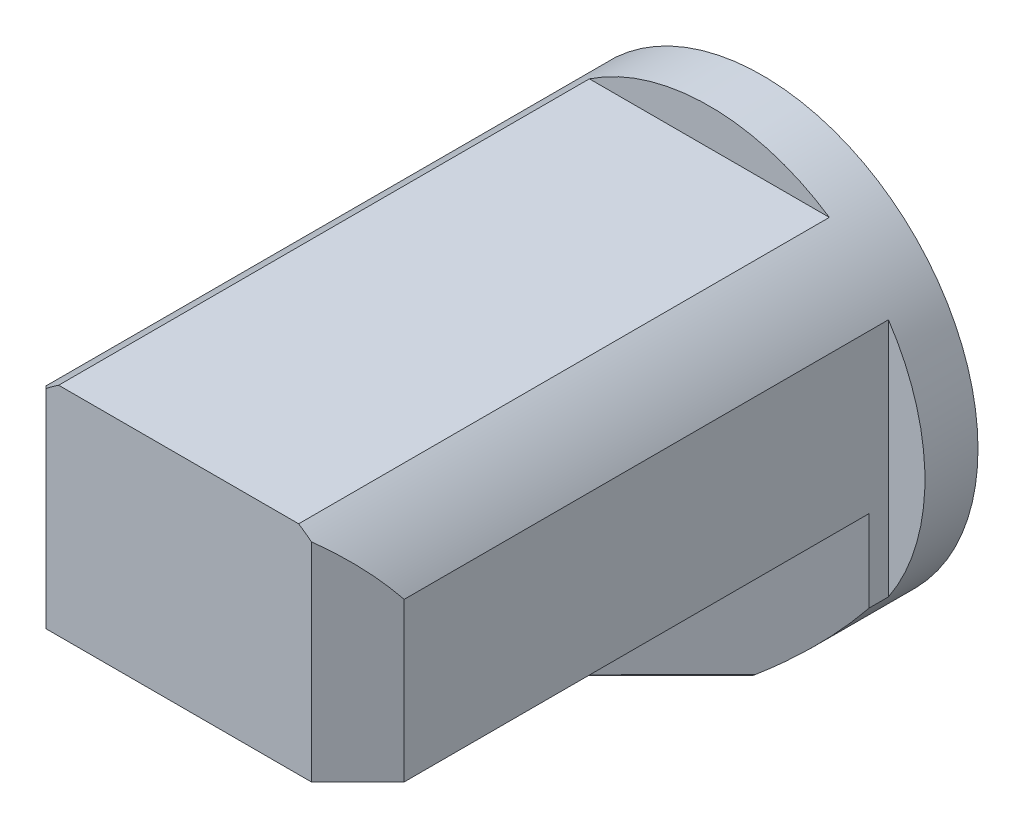
SolidWorks part; units mm, degrees
material "Cast Stainless Steel"
ref_plane "Front Plane" through (0, 0, 0) normal (0, 0, 1) x (1, 0, 0)
ref_plane "Top Plane" through (0, 0, 0) normal (0, 1, 0) x (1, 0, 0)
ref_plane "Right Plane" through (0, 0, 0) normal (1, 0, 0) x (0, 0, -1)
sketch "Sketch3" plane through (0, 0, 0) normal (0, 1, 0) x (1, 0, 0)
  circle A0 centre (0, 0) radius 130
extrude "Boss-Extrude1" add sketch "Sketch3" along normal blind 352
sketch "Sketch11" plane through (0, 352, 0) normal (0, 1, 0) x (1, 0, 0)
  line L0 (0, 0) -> (0, -108)
  line L1 (-72.3602, -108) -> (72.3602, -108)
  line L2 (0, 0) -> (-54.0967, 0)
  line L3 (-72.3602, 108) -> (72.3602, 108)
  line L4 (0, 0) -> (0, 40.1674)
  line L5 (0, 0) -> (108, 0)
  line L6 (108, 72.3602) -> (108, -72.3602)
  line L7 (-108, 72.3602) -> (-108, -72.3602)
  circle A0 centre (0, 0) radius 130 construction
  circle A2 centre (0, 0) radius 130
  circle A3 centre (0, 0) radius 130
  circle M1 centre (0, 0) radius 130
  dimension "D1" = 0
extrude "Cut-Extrude2" cut sketch "Sketch11" against normal blind 320 contours L1 M1 | L3 M1 region at (0, 352, 116.8671) region at (0, 352, -116.8671)
extrude "Cut-Extrude3" cut sketch "Sketch11<4>" against normal blind 320 contours L7 M1 | L6 M1 region at (116.8671, 352, 0) region at (-116.8671, 352, 0)
sketch "Sketch11<4>" plane through (0, 352, 0) normal (0, 1, 0) x (1, 0, 0) same geometry as "Sketch11"
sketch "Sketch12" plane through (-108, 0, 0) normal (-1, 0, 0) x (0, 0, 1)
  line L0 (0, 32) -> (0, 137)
  line L1 (-72.3602, 32) -> (72.3602, 32) construction
  line L2 (-72.3602, 137) -> (72.3602, 137)
  line L3 (-72.3602, 32) -> (-72.3602, 352) construction
  line L4 (72.3602, 32) -> (72.3602, 352) construction
  line L5 (72.3602, 32) -> (72.3602, 352)
  line L6 (-72.3602, 32) -> (-72.3602, 352)
  line L7 (-72.3602, 352) -> (72.3602, 352) construction
  line L8 (-72.3602, 352) -> (72.3602, 352)
  line L13 (72.3602, 352) -> (-72.3602, 352)
  line L14 (-72.3602, 352) -> (-72.3602, 32)
  line L15 (-72.3602, 32) -> (72.3602, 32)
  line L16 (72.3602, 32) -> (72.3602, 352)
  line L17 (72.3602, 352) -> (-72.3602, 352)
  line L18 (-72.3602, 352) -> (-72.3602, 32)
  line L19 (-72.3602, 32) -> (72.3602, 32)
  line L20 (72.3602, 32) -> (72.3602, 352)
  line M2 (72.3602, 352) -> (-72.3602, 352)
  line M3 (-72.3602, 352) -> (-72.3602, 32)
  line M5 (72.3602, 32) -> (72.3602, 352)
  dimension "D1" = 0
extrude "Cut-Extrude4" cut sketch "Sketch12" against normal blind 85 contours L2 M3 M5 M2 region at (-108, 244.5, 0)
sketch "Sketch14" plane through (-108, 0, 0) normal (-1, 0, 0) x (0, 0, 1)
  line L0 (-14.6151, 137) -> (14.6151, 137)
  line L1 (-72.3602, 137) -> (72.3602, 137) construction
  line L2 (14.6151, 137) -> (72.3602, 79.2549)
  line L3 (72.3602, 32) -> (72.3602, 137) construction
  line L4 (0, 137) -> (0, 116.7059)
  line L5 (-14.6151, 137) -> (-72.3602, 79.2549)
  line L10 (72.3602, 137) -> (-72.3602, 137)
  line L11 (-72.3602, 137) -> (-72.3602, 32)
  line L12 (-72.3602, 32) -> (72.3602, 32)
  line L13 (72.3602, 32) -> (72.3602, 137)
  line L14 (72.3602, 137) -> (-72.3602, 137)
  line L15 (-72.3602, 137) -> (-72.3602, 32)
  line L16 (-72.3602, 32) -> (72.3602, 32)
  line L17 (72.3602, 32) -> (72.3602, 137)
  line M8 (72.3602, 137) -> (-72.3602, 137)
  line M9 (-72.3602, 137) -> (-72.3602, 32)
  line M11 (72.3602, 32) -> (72.3602, 137)
  dimension "D1" = 0
extrude "Cut-Extrude5" cut sketch "Sketch14" against normal blind 85 contours L5 M8 M9 | L2 M8 M11 region at (-108, 117.7516, -53.1118) region at (-108, 117.7516, 53.1118)
sketch "Sketch15" plane through (0, 352, 0) normal (0, 1, 0) x (1, 0, 0)
  line L0 (-23, -72.3602) -> (-23, -108)
  line L1 (-72.3602, -108) -> (72.3602, -108) construction
  line L2 (-23, 72.3602) -> (-23, 108)
  line L3 (-72.3602, 108) -> (72.3602, 108) construction
  line L10 (-108, 72.3602) -> (-23, 72.3602)
  line L11 (-23, 72.3602) -> (-23, -72.3602)
  line L12 (-23, -72.3602) -> (-108, -72.3602)
  line L13 (-72.3602, -108) -> (72.3602, -108)
  line L14 (108, -72.3602) -> (108, 72.3602)
  line L15 (72.3602, 108) -> (-72.3602, 108)
  line L16 (-108, 72.3602) -> (-23, 72.3602)
  line L17 (-23, 72.3602) -> (-23, -72.3602)
  line L18 (-23, -72.3602) -> (-108, -72.3602)
  line L19 (-72.3602, -108) -> (72.3602, -108)
  line L20 (108, -72.3602) -> (108, 72.3602)
  line L21 (72.3602, 108) -> (-72.3602, 108)
  arc A4 (-108, -72.3602) -> (-72.3602, -108) centre (0, 0) ccw
  arc A5 (72.3602, -108) -> (108, -72.3602) centre (0, 0) ccw
  arc A6 (108, 72.3602) -> (72.3602, 108) centre (0, 0) ccw
  arc A7 (-72.3602, 108) -> (-108, 72.3602) centre (0, 0) ccw
  arc A8 (-108, -72.3602) -> (-72.3602, -108) centre (0, 0) ccw
  arc A9 (72.3602, -108) -> (108, -72.3602) centre (0, 0) ccw
  arc A10 (108, 72.3602) -> (72.3602, 108) centre (0, 0) ccw
  arc A11 (-72.3602, 108) -> (-108, 72.3602) centre (0, 0) ccw
  line M11 (-108, 72.3602) -> (-23, 72.3602)
  line M13 (-23, -72.3602) -> (-108, -72.3602)
  arc M14 (-108, -72.3602) -> (-72.3602, -108) centre (0, 0) ccw
  line M15 (-72.3602, -108) -> (72.3602, -108)
  line M19 (72.3602, 108) -> (-72.3602, 108)
  arc M20 (-72.3602, 108) -> (-108, 72.3602) centre (0, 0) ccw
  dimension "D1" = 0
extrude "Cut-Extrude7" cut sketch "Sketch15" against normal up to surface (308.3849 mm away) contours L2 M11 M19 M20 region at (-58.5006, 352, -88.6807) up to face at (-65.5, 108.1274, -43.4877)
extrude "Cut-Extrude8" cut sketch "Sketch15<4>" against normal up to surface (308.3849 mm away) contours L0 M13 M14 M15 region at (-58.5006, 352, 88.6807) up to face at (-65.5, 108.1274, 43.4877)
sketch "Sketch15<4>" plane through (0, 352, 0) normal (0, 1, 0) x (1, 0, 0) same geometry as "Sketch15"
sketch "Sketch18" plane through (-23, 0, 0) normal (-1, 0, 0) x (0, 0, 1)
  line L0 (-80, 352) -> (80, 352)
  line L1 (108, 352) -> (-108, 352) construction
  line L2 (80, 352) -> (108, 324)
  line L3 (108, 43.6151) -> (108, 352) construction
  line L4 (0, 352) -> (0, 328.1223)
  line L5 (-80, 352) -> (-108, 324)
  line L12 (108, 352) -> (-108, 352)
  line L13 (-108, 352) -> (-108, 43.6151)
  line L14 (-108, 43.6151) -> (-14.6151, 137)
  line L15 (-14.6151, 137) -> (14.6151, 137)
  line L16 (14.6151, 137) -> (108, 43.6151)
  line L17 (108, 43.6151) -> (108, 352)
  line L18 (108, 352) -> (-108, 352)
  line L19 (-108, 352) -> (-108, 43.6151)
  line L20 (-108, 43.6151) -> (-14.6151, 137)
  line L21 (-14.6151, 137) -> (14.6151, 137)
  line L22 (14.6151, 137) -> (108, 43.6151)
  line L23 (108, 43.6151) -> (108, 352)
  line M4 (108, 352) -> (-108, 352)
  line M5 (-108, 352) -> (-108, 43.6151)
  line M9 (108, 43.6151) -> (108, 352)
  dimension "D1" = 0
extrude "Cut-Extrude9" cut sketch "Sketch18" against normal blind 285 contours L5 M4 M5 | L2 M4 M9 region at (-23, 342.6667, -98.6667) region at (-23, 342.6667, 98.6667)
sketch "Sketch19" plane through (108, 0, 0) normal (1, 0, 0) x (0, 0, -1)
  line L0 (0, 352) -> (0, 242)
  line L1 (72.3602, 352) -> (-72.3602, 352) construction
  circle A0 centre (0, 242) radius 65
  dimension "D1" = 130
sketch "Sketch22" plane through (-108, 0, 0) normal (-1, 0, 0) x (0, 0, 1)
  line L0 (-14.6151, 137) -> (-72.3602, 79.2549) construction
  line L1 (-43.4877, 108.1274) -> (16.5123, 108.1274)
  line L2 (-43.4877, 108.1274) -> (-43.4877, 48.1274)
  line L3 (-43.4877, 48.1274) -> (16.5123, 48.1274)
  line L4 (16.5123, 108.1274) -> (16.5123, 48.1274)
  line L12 (14.6151, 137) -> (-14.6151, 137)
  line L13 (-14.6151, 137) -> (-72.3602, 79.2549)
  line L14 (-72.3602, 79.2549) -> (-72.3602, 32)
  line L15 (-72.3602, 32) -> (72.3602, 32)
  line L16 (72.3602, 32) -> (72.3602, 79.2549)
  line L17 (72.3602, 79.2549) -> (14.6151, 137)
  line L18 (14.6151, 137) -> (-14.6151, 137)
  line L19 (-14.6151, 137) -> (-72.3602, 79.2549)
  line L20 (-72.3602, 79.2549) -> (-72.3602, 32)
  line L21 (-72.3602, 32) -> (72.3602, 32)
  line L22 (72.3602, 32) -> (72.3602, 79.2549)
  line L23 (72.3602, 79.2549) -> (14.6151, 137)
  dimension "D1" = 0
extrude "Boss-Extrude3" add sketch "Sketch22" along normal blind 2 contours L4 L1 L2 L3 region at (-108, 78.1274, -13.4877)
fillet "Fillet1" radius 3 1 edges at (-109, 108.1274, -43.4877)
fillet "Fillet2" radius 3 3 edges at (-109, 48.1274, -43.4877) (-109, 48.1274, 16.5123) (-109, 108.1274, 16.5123)
fillet "Fillet4" radius 1 3 edges at (-108, 122.5637, -29.0514) (-108, 93.6912, -57.9239) (-108, 108.1274, 43.4877)
fillet "Fillet5" radius 1 8 edges at (-108, 107.2488, -42.609) (-108, 78.1274, -43.4877) (-108, 49.0061, -42.609) (-108, 48.1274, -13.4877) (-108, 49.0061, 15.6337) (-108, 78.1274, 16.5123) (-108, 107.2488, 15.6337) (-108, 108.1274, -13.4877)
move or copy body "Body-Move/Copy2" bodies to move or copy 113 copy no rotation origin (0, 0, 0) rotation axis (1, 0, 0) rotation angle 90
ref_plane "Plane1" through (0, 0, 362) normal (0, 0, 1) x (1, 0, 0)
sketch "Sketch29" plane through (0, 108, 0) normal (0, 1, 0) x (1, 0, 0)
  line L1 (56.7496, -229) -> (-6, -229)
  line L2 (56.7496, -229) -> (56.7496, -49)
  line L3 (56.7496, -49) -> (-6, -49)
  line L4 (-6, -229) -> (-6, -49)
  line L6 (-23, -324) -> (72.3602, -324)
  line L7 (-23, -324) -> (72.3602, -324)
  line L8 (72.3602, -324) -> (72.3602, -32)
  line L9 (72.3602, -324) -> (72.3602, -32)
  line L10 (72.3602, -32) -> (-72.3602, -32)
  line L11 (72.3602, -32) -> (-72.3602, -32)
  line L22 (-72.3602, -32) -> (-72.3602, -43.6151)
  line L23 (-72.3602, -32) -> (-72.3602, -43.6151)
  line L24 (-72.3602, -43.6151) -> (-23, -43.6151)
  line L25 (-72.3602, -43.6151) -> (-23, -43.6151)
  line L26 (-23, -43.6151) -> (-23, -324)
  line L27 (-23, -43.6151) -> (-23, -324)
  dimension "D5" = 180
  dimension "D1" = 0
sketch "Sketch31" plane through (-110, 0, 0) normal (-1, 0, 0) x (0, 0, 1)
  line L4 (105.1274, 43.4877) -> (51.1274, 43.4877)
  line L5 (48.1274, 40.4877) -> (48.1274, -13.5123)
  line L6 (51.1274, -16.5123) -> (105.1274, -16.5123)
  line L7 (108.1274, -13.5123) -> (108.1274, 40.4877)
  line L8 (105.1274, 43.4877) -> (51.1274, 43.4877)
  line L9 (48.1274, 40.4877) -> (48.1274, -13.5123)
  line L10 (51.1274, -16.5123) -> (105.1274, -16.5123)
  line L11 (108.1274, -13.5123) -> (108.1274, 40.4877)
  circle A0 centre (78.1274, 13.4877) radius 30
  circle A1 centre (78.1274, 13.4877) radius 20
  arc A4 (51.1274, 43.4877) -> (48.1274, 40.4877) centre (51.1274, 40.4877) ccw
  arc A5 (48.1274, -13.5123) -> (51.1274, -16.5123) centre (51.1274, -13.5123) ccw
  arc A6 (105.1274, -16.5123) -> (108.1274, -13.5123) centre (105.1274, -13.5123) ccw
  arc A7 (108.1274, 40.4877) -> (105.1274, 43.4877) centre (105.1274, 40.4877) ccw
  arc A8 (51.1274, 43.4877) -> (48.1274, 40.4877) centre (51.1274, 40.4877) ccw
  arc A9 (48.1274, -13.5123) -> (51.1274, -16.5123) centre (51.1274, -13.5123) ccw
  arc A10 (105.1274, -16.5123) -> (108.1274, -13.5123) centre (105.1274, -13.5123) ccw
  arc A11 (108.1274, 40.4877) -> (105.1274, 43.4877) centre (105.1274, 40.4877) ccw
  dimension "D1" = 0
  dimension "D2" = 10
move or copy body "Body-Move/Copy3" bodies to move or copy 116 copy no rotation origin (0, 0, 0) rotation axis (0, 0, -1) rotation angle 90
move or copy body "Body-Move/Copy4" bodies to move or copy 126 copy no rotation origin (0, 0, 0) rotation axis (0, 0, 1) rotation angle 180
